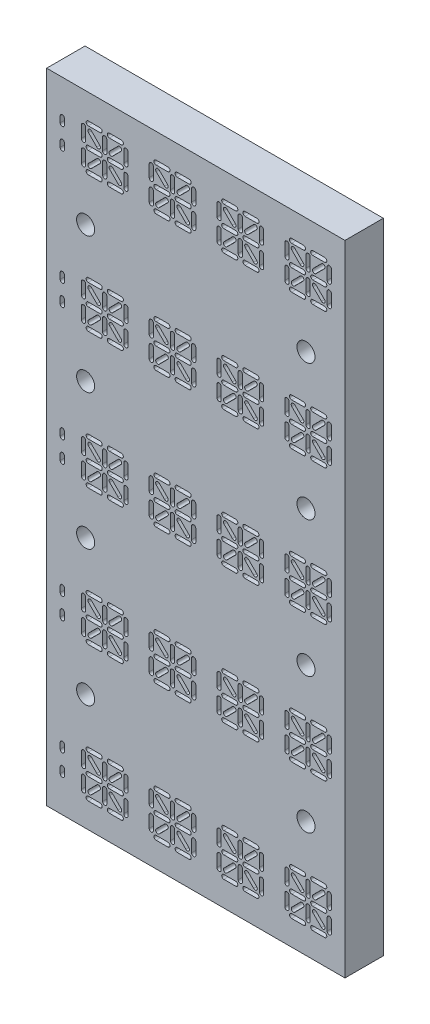
SolidWorks part; units mm, degrees
material "ABS PC"
ref_plane "Front Plane" through (0, 0, 0) normal (0, 0, 1) x (1, 0, 0)
ref_plane "Top Plane" through (0, 0, 0) normal (0, 1, 0) x (1, 0, 0)
ref_plane "Right Plane" through (0, 0, 0) normal (1, 0, 0) x (0, 0, -1)
sketch "Sketch1" plane through (0, 0, 0) normal (0, 0, 1) x (1, 0, 0)
  line L0 (265.9975, 197.0179) -> (342.1693, 194.9479) construction
  line L1 (297.418, 228.3826) -> (298.307, 228.3826) construction
  line L2 (297.418, 228.3826) -> (300.593, 228.3826) construction
  line L3 (302.371, 228.3826) -> (302.371, 231.5576) construction
  line L4 (296.7097, 229.0811) -> (296.7097, 229.9701) construction
  line L5 (296.7097, 230.8591) -> (296.7097, 234.0341) construction
  line L6 (296.7097, 234.0341) -> (299.8847, 234.0341) construction
  line L7 (296.7097, 234.0341) -> (297.0639, 234.3834) construction
  line L8 (296.7097, 234.0341) -> (297.418, 234.7326) construction
  line L9 (299.196, 231.5576) -> (300.593, 231.5576) construction
  line L10 (297.0639, 234.3834) -> (299.5404, 231.9069) construction
  line L11 (296.7097, 232.2561) -> (296.7097, 230.8591) construction
  line L12 (297.418, 231.5576) -> (296.7097, 231.5576) construction
  line L13 (299.8847, 232.2561) -> (299.196, 231.5576) construction
  line L14 (299.8945, 231.5576) -> (298.9307, 232.5165) construction
  line L15 (299.8945, 231.5576) -> (300.8534, 232.5214) construction
  line L16 (297.418, 234.7326) -> (307.578, 234.7326) construction
  line L17 (293.5347, 230.4146) -> (293.5347, 229.5256) construction
  line L18 (293.5347, 232.7006) -> (293.5347, 230.4146) construction
  line L19 (335.8892, 225.6039) -> (291.1852, 225.6039)
  line L20 (335.8892, 225.6039) -> (335.8892, 237.5114)
  line L21 (335.8892, 237.5114) -> (291.1852, 237.5114)
  line L22 (291.1852, 225.6039) -> (291.1852, 237.5114)
  line L23 (335.8892, 225.6039) -> (291.1852, 237.5114) construction
  line L24 (335.8892, 237.5114) -> (291.1852, 225.6039) construction
  line L25 (333.5397, 232.2561) -> (333.5397, 230.8591) construction
  line L26 (293.5347, 231.5576) -> (333.5397, 231.5576) construction
  line L27 (297.418, 228.3826) -> (299.196, 228.3826) construction
  line L32 (297.418, 228.7001) -> (299.196, 228.7001)
  line L33 (297.418, 228.0651) -> (299.196, 228.0651)
  line L34 (300.593, 228.3826) -> (302.371, 228.3826) construction
  line L35 (300.593, 228.7001) -> (302.371, 228.7001)
  line L36 (300.593, 228.0651) -> (302.371, 228.0651)
  line L37 (302.1155, 229.3415) -> (300.8582, 230.5987) construction
  line L38 (301.891, 229.117) -> (300.6337, 230.3742)
  line L39 (302.34, 229.566) -> (301.0827, 230.8233)
  line L40 (299.8847, 229.0811) -> (299.8847, 230.8591) construction
  line L41 (299.5672, 229.0811) -> (299.5672, 230.8591)
  line L42 (300.2022, 229.0811) -> (300.2022, 230.8591)
  line L43 (298.9356, 230.5939) -> (297.6784, 229.3366) construction
  line L44 (299.1601, 230.3694) -> (297.9029, 229.1121)
  line L45 (298.7111, 230.8184) -> (297.4539, 229.5611)
  line L46 (296.7097, 229.0811) -> (296.7097, 230.8591) construction
  line L47 (296.3922, 229.0811) -> (296.3922, 230.8591)
  line L48 (297.0272, 229.0811) -> (297.0272, 230.8591)
  line L49 (303.0597, 230.8591) -> (303.0597, 229.0811) construction
  line L50 (303.3772, 230.8591) -> (303.3772, 229.0811)
  line L51 (302.7422, 230.8591) -> (302.7422, 229.0811)
  line L52 (302.371, 231.5576) -> (300.593, 231.5576) construction
  line L53 (302.371, 231.2401) -> (300.593, 231.2401)
  line L54 (302.371, 231.8751) -> (300.593, 231.8751)
  line L55 (303.0597, 234.0341) -> (303.0597, 232.2561) construction
  line L56 (303.3772, 234.0341) -> (303.3772, 232.2561)
  line L57 (302.7422, 234.0341) -> (302.7422, 232.2561)
  line L58 (302.1106, 233.7786) -> (300.8534, 232.5214) construction
  line L59 (302.3351, 233.5541) -> (301.0779, 232.2969)
  line L60 (301.8861, 234.0031) -> (300.6289, 232.7459)
  line L61 (302.371, 234.7326) -> (300.593, 234.7326) construction
  line L62 (302.371, 234.4151) -> (300.593, 234.4151)
  line L63 (302.371, 235.0501) -> (300.593, 235.0501)
  line L64 (299.8847, 234.0341) -> (299.8847, 232.2561) construction
  line L65 (300.2022, 234.0341) -> (300.2022, 232.2561)
  line L66 (299.5672, 234.0341) -> (299.5672, 232.2561)
  line L67 (297.418, 231.5576) -> (299.196, 231.5576) construction
  line L68 (297.418, 231.8751) -> (299.196, 231.8751)
  line L69 (297.418, 231.2401) -> (299.196, 231.2401)
  line L70 (298.9307, 232.5165) -> (297.6735, 233.7737) construction
  line L71 (298.7062, 232.292) -> (297.449, 233.5492)
  line L72 (299.1552, 232.741) -> (297.898, 233.9983)
  line L73 (296.7097, 232.2561) -> (296.7097, 234.0341) construction
  line L74 (296.3922, 232.2561) -> (296.3922, 234.0341)
  line L75 (297.0272, 232.2561) -> (297.0272, 234.0341)
  line L76 (297.418, 234.7326) -> (299.196, 234.7326) construction
  line L77 (297.418, 235.0501) -> (299.196, 235.0501)
  line L78 (297.418, 234.4151) -> (299.196, 234.4151)
  line L79 (293.5347, 232.7006) -> (293.5347, 233.5896) construction
  line L80 (293.2172, 232.7006) -> (293.2172, 233.5896)
  line L81 (293.8522, 232.7006) -> (293.8522, 233.5896)
  line L82 (293.5347, 230.4146) -> (293.5347, 229.5256) construction
  line L83 (293.8522, 230.4146) -> (293.8522, 229.5256)
  line L84 (293.2172, 230.4146) -> (293.2172, 229.5256)
  line L85 (307.578, 228.3826) -> (309.356, 228.3826) construction
  line L86 (307.578, 228.7001) -> (309.356, 228.7001)
  line L87 (307.578, 228.0651) -> (309.356, 228.0651)
  line L88 (310.753, 228.3826) -> (312.531, 228.3826) construction
  line L89 (310.753, 228.7001) -> (312.531, 228.7001)
  line L90 (310.753, 228.0651) -> (312.531, 228.0651)
  line L91 (312.2755, 229.3415) -> (311.0182, 230.5987) construction
  line L92 (312.051, 229.117) -> (310.7937, 230.3742)
  line L93 (312.5, 229.566) -> (311.2427, 230.8233)
  line L94 (310.0447, 229.0811) -> (310.0447, 230.8591) construction
  line L95 (309.7272, 229.0811) -> (309.7272, 230.8591)
  line L96 (310.3622, 229.0811) -> (310.3622, 230.8591)
  line L97 (309.0956, 230.5939) -> (307.8384, 229.3366) construction
  line L98 (309.3201, 230.3694) -> (308.0629, 229.1121)
  line L99 (308.8711, 230.8184) -> (307.6139, 229.5611)
  line L100 (306.8697, 229.0811) -> (306.8697, 230.8591) construction
  line L101 (306.5522, 229.0811) -> (306.5522, 230.8591)
  line L102 (307.1872, 229.0811) -> (307.1872, 230.8591)
  line L103 (313.2197, 230.8591) -> (313.2197, 229.0811) construction
  line L104 (313.5372, 230.8591) -> (313.5372, 229.0811)
  line L105 (312.9022, 230.8591) -> (312.9022, 229.0811)
  line L106 (312.531, 231.5576) -> (310.753, 231.5576) construction
  line L107 (312.531, 231.2401) -> (310.753, 231.2401)
  line L108 (312.531, 231.8751) -> (310.753, 231.8751)
  line L109 (313.2197, 234.0341) -> (313.2197, 232.2561) construction
  line L110 (313.5372, 234.0341) -> (313.5372, 232.2561)
  line L111 (312.9022, 234.0341) -> (312.9022, 232.2561)
  line L112 (312.2706, 233.7786) -> (311.0134, 232.5214) construction
  line L113 (312.4951, 233.5541) -> (311.2379, 232.2969)
  line L114 (312.0461, 234.0031) -> (310.7889, 232.7459)
  line L115 (312.531, 234.7326) -> (310.753, 234.7326) construction
  line L116 (312.531, 234.4151) -> (310.753, 234.4151)
  line L117 (312.531, 235.0501) -> (310.753, 235.0501)
  line L118 (310.0447, 234.0341) -> (310.0447, 232.2561) construction
  line L119 (310.3622, 234.0341) -> (310.3622, 232.2561)
  line L120 (309.7272, 234.0341) -> (309.7272, 232.2561)
  line L121 (307.578, 231.5576) -> (309.356, 231.5576) construction
  line L122 (307.578, 231.8751) -> (309.356, 231.8751)
  line L123 (307.578, 231.2401) -> (309.356, 231.2401)
  line L124 (309.0907, 232.5165) -> (307.8335, 233.7737) construction
  line L125 (308.8662, 232.292) -> (307.609, 233.5492)
  line L126 (309.3152, 232.741) -> (308.058, 233.9983)
  line L127 (306.8697, 232.2561) -> (306.8697, 234.0341) construction
  line L128 (306.5522, 232.2561) -> (306.5522, 234.0341)
  line L129 (307.1872, 232.2561) -> (307.1872, 234.0341)
  line L130 (307.578, 234.7326) -> (309.356, 234.7326) construction
  line L131 (307.578, 235.0501) -> (309.356, 235.0501)
  line L132 (307.578, 234.4151) -> (309.356, 234.4151)
  line L133 (317.738, 228.3826) -> (319.516, 228.3826) construction
  line L134 (317.738, 228.7001) -> (319.516, 228.7001)
  line L135 (317.738, 228.0651) -> (319.516, 228.0651)
  line L136 (320.913, 228.3826) -> (322.691, 228.3826) construction
  line L137 (320.913, 228.7001) -> (322.691, 228.7001)
  line L138 (320.913, 228.0651) -> (322.691, 228.0651)
  line L139 (322.4355, 229.3415) -> (321.1782, 230.5987) construction
  line L140 (322.211, 229.117) -> (320.9537, 230.3742)
  line L141 (322.66, 229.566) -> (321.4027, 230.8233)
  line L142 (320.2047, 229.0811) -> (320.2047, 230.8591) construction
  line L143 (319.8872, 229.0811) -> (319.8872, 230.8591)
  line L144 (320.5222, 229.0811) -> (320.5222, 230.8591)
  line L145 (319.2556, 230.5939) -> (317.9984, 229.3366) construction
  line L146 (319.4801, 230.3694) -> (318.2229, 229.1121)
  line L147 (319.0311, 230.8184) -> (317.7739, 229.5611)
  line L148 (317.0297, 229.0811) -> (317.0297, 230.8591) construction
  line L149 (316.7122, 229.0811) -> (316.7122, 230.8591)
  line L150 (317.3472, 229.0811) -> (317.3472, 230.8591)
  line L151 (323.3797, 230.8591) -> (323.3797, 229.0811) construction
  line L152 (323.6972, 230.8591) -> (323.6972, 229.0811)
  line L153 (323.0622, 230.8591) -> (323.0622, 229.0811)
  line L154 (322.691, 231.5576) -> (320.913, 231.5576) construction
  line L155 (322.691, 231.2401) -> (320.913, 231.2401)
  line L156 (322.691, 231.8751) -> (320.913, 231.8751)
  line L157 (323.3797, 234.0341) -> (323.3797, 232.2561) construction
  line L158 (323.6972, 234.0341) -> (323.6972, 232.2561)
  line L159 (323.0622, 234.0341) -> (323.0622, 232.2561)
  line L160 (322.4306, 233.7786) -> (321.1734, 232.5214) construction
  line L161 (322.6551, 233.5541) -> (321.3979, 232.2969)
  line L162 (322.2061, 234.0031) -> (320.9489, 232.7459)
  line L163 (322.691, 234.7326) -> (320.913, 234.7326) construction
  line L164 (322.691, 234.4151) -> (320.913, 234.4151)
  line L165 (322.691, 235.0501) -> (320.913, 235.0501)
  line L166 (320.2047, 234.0341) -> (320.2047, 232.2561) construction
  line L167 (320.5222, 234.0341) -> (320.5222, 232.2561)
  line L168 (319.8872, 234.0341) -> (319.8872, 232.2561)
  line L169 (317.738, 231.5576) -> (319.516, 231.5576) construction
  line L170 (317.738, 231.8751) -> (319.516, 231.8751)
  line L171 (317.738, 231.2401) -> (319.516, 231.2401)
  line L172 (319.2507, 232.5165) -> (317.9935, 233.7737) construction
  line L173 (319.0262, 232.292) -> (317.769, 233.5492)
  line L174 (319.4752, 232.741) -> (318.218, 233.9983)
  line L175 (317.0297, 232.2561) -> (317.0297, 234.0341) construction
  line L176 (316.7122, 232.2561) -> (316.7122, 234.0341)
  line L177 (317.3472, 232.2561) -> (317.3472, 234.0341)
  line L178 (317.738, 234.7326) -> (319.516, 234.7326) construction
  line L179 (317.738, 235.0501) -> (319.516, 235.0501)
  line L180 (317.738, 234.4151) -> (319.516, 234.4151)
  line L181 (327.898, 228.3826) -> (329.676, 228.3826) construction
  line L182 (327.898, 228.7001) -> (329.676, 228.7001)
  line L183 (327.898, 228.0651) -> (329.676, 228.0651)
  line L184 (331.073, 228.3826) -> (332.851, 228.3826) construction
  line L185 (331.073, 228.7001) -> (332.851, 228.7001)
  line L186 (331.073, 228.0651) -> (332.851, 228.0651)
  line L187 (332.5955, 229.3415) -> (331.3382, 230.5987) construction
  line L188 (332.371, 229.117) -> (331.1137, 230.3742)
  line L189 (332.82, 229.566) -> (331.5627, 230.8233)
  line L190 (330.3647, 229.0811) -> (330.3647, 230.8591) construction
  line L191 (330.0472, 229.0811) -> (330.0472, 230.8591)
  line L192 (330.6822, 229.0811) -> (330.6822, 230.8591)
  line L193 (329.4156, 230.5939) -> (328.1584, 229.3366) construction
  line L194 (329.6401, 230.3694) -> (328.3829, 229.1121)
  line L195 (329.1911, 230.8184) -> (327.9339, 229.5611)
  line L196 (327.1897, 229.0811) -> (327.1897, 230.8591) construction
  line L197 (326.8722, 229.0811) -> (326.8722, 230.8591)
  line L198 (327.5072, 229.0811) -> (327.5072, 230.8591)
  line L199 (333.5397, 230.8591) -> (333.5397, 229.0811) construction
  line L200 (333.8572, 230.8591) -> (333.8572, 229.0811)
  line L201 (333.2222, 230.8591) -> (333.2222, 229.0811)
  line L202 (332.851, 231.5576) -> (331.073, 231.5576) construction
  line L203 (332.851, 231.2401) -> (331.073, 231.2401)
  line L204 (332.851, 231.8751) -> (331.073, 231.8751)
  line L205 (333.5397, 234.0341) -> (333.5397, 232.2561) construction
  line L206 (333.8572, 234.0341) -> (333.8572, 232.2561)
  line L207 (333.2222, 234.0341) -> (333.2222, 232.2561)
  line L208 (332.5906, 233.7786) -> (331.3334, 232.5214) construction
  line L209 (332.8151, 233.5541) -> (331.5579, 232.2969)
  line L210 (332.3661, 234.0031) -> (331.1089, 232.7459)
  line L211 (332.851, 234.7326) -> (331.073, 234.7326) construction
  line L212 (332.851, 234.4151) -> (331.073, 234.4151)
  line L213 (332.851, 235.0501) -> (331.073, 235.0501)
  line L214 (330.3647, 234.0341) -> (330.3647, 232.2561) construction
  line L215 (330.6822, 234.0341) -> (330.6822, 232.2561)
  line L216 (330.0472, 234.0341) -> (330.0472, 232.2561)
  line L217 (327.898, 231.5576) -> (329.676, 231.5576) construction
  line L218 (327.898, 231.8751) -> (329.676, 231.8751)
  line L219 (327.898, 231.2401) -> (329.676, 231.2401)
  line L220 (329.4107, 232.5165) -> (328.1535, 233.7737) construction
  line L221 (329.1862, 232.292) -> (327.929, 233.5492)
  line L222 (329.6352, 232.741) -> (328.378, 233.9983)
  line L223 (327.1897, 232.2561) -> (327.1897, 234.0341) construction
  line L224 (326.8722, 232.2561) -> (326.8722, 234.0341)
  line L225 (327.5072, 232.2561) -> (327.5072, 234.0341)
  line L226 (327.898, 234.7326) -> (329.676, 234.7326) construction
  line L227 (327.898, 235.0501) -> (329.676, 235.0501)
  line L228 (327.898, 234.4151) -> (329.676, 234.4151)
  line L229 (296.7097, 229.0811) -> (306.8697, 229.0811) construction
  circle A0 centre (297.418, 228.3826) radius 0.3175 construction
  circle A3 centre (298.307, 228.3826) radius 0.3175 construction
  circle A4 centre (299.196, 228.3826) radius 0.3175 construction
  circle A5 centre (300.593, 228.3826) radius 0.3175 construction
  circle A6 centre (301.482, 228.3826) radius 0.3175 construction
  circle A7 centre (302.371, 228.3826) radius 0.3175 construction
  circle A8 centre (302.371, 231.5576) radius 0.3175 construction
  circle A9 centre (301.482, 231.5576) radius 0.3175 construction
  circle A10 centre (300.593, 231.5576) radius 0.3175 construction
  circle A11 centre (299.196, 231.5576) radius 0.3175 construction
  circle A12 centre (298.307, 231.5576) radius 0.3175 construction
  circle A13 centre (297.418, 231.5576) radius 0.3175 construction
  circle A14 centre (302.371, 234.7326) radius 0.3175 construction
  circle A15 centre (301.482, 234.7326) radius 0.3175 construction
  circle A16 centre (300.593, 234.7326) radius 0.3175 construction
  circle A17 centre (299.196, 234.7326) radius 0.3175 construction
  circle A18 centre (298.307, 234.7326) radius 0.3175 construction
  circle A19 centre (297.418, 234.7326) radius 0.3175 construction
  circle A20 centre (296.7097, 229.0811) radius 0.3175 construction
  circle A21 centre (296.7097, 229.9701) radius 0.3175 construction
  circle A22 centre (296.7097, 230.8591) radius 0.3175 construction
  circle A23 centre (296.7097, 234.0341) radius 0.3175 construction
  circle A24 centre (296.7097, 233.1451) radius 0.3175 construction
  circle A25 centre (296.7097, 232.2561) radius 0.3175 construction
  circle A26 centre (299.8847, 234.0341) radius 0.3175 construction
  circle A27 centre (299.8847, 233.1451) radius 0.3175 construction
  circle A28 centre (299.8847, 232.2561) radius 0.3175 construction
  circle A29 centre (299.8847, 230.8591) radius 0.3175 construction
  circle A30 centre (299.8847, 229.9701) radius 0.3175 construction
  circle A31 centre (299.8847, 229.0811) radius 0.3175 construction
  circle A32 centre (297.6735, 233.7737) radius 0.3175 construction
  circle A33 centre (298.3021, 233.1451) radius 0.3175 construction
  circle A34 centre (298.9307, 232.5165) radius 0.3175 construction
  circle A35 centre (303.0597, 234.0341) radius 0.3175 construction
  circle A36 centre (303.0597, 233.1451) radius 0.3175 construction
  circle A37 centre (303.0597, 232.2561) radius 0.3175 construction
  circle A38 centre (303.0597, 230.8591) radius 0.3175 construction
  circle A39 centre (303.0597, 229.9701) radius 0.3175 construction
  circle A40 centre (303.0597, 229.0811) radius 0.3175 construction
  circle A41 centre (300.8534, 232.5214) radius 0.3175 construction
  circle A42 centre (301.482, 233.15) radius 0.3175 construction
  circle A43 centre (302.1106, 233.7786) radius 0.3175 construction
  circle A44 centre (300.8582, 230.5987) radius 0.3175 construction
  circle A45 centre (301.4869, 229.9701) radius 0.3175 construction
  circle A46 centre (302.1155, 229.3415) radius 0.3175 construction
  circle A47 centre (298.9356, 230.5939) radius 0.3175 construction
  circle A48 centre (298.307, 229.9653) radius 0.3175 construction
  circle A49 centre (297.6784, 229.3366) radius 0.3175 construction
  circle A50 centre (307.578, 234.7326) radius 0.3175 construction
  circle A51 centre (306.8697, 234.0341) radius 0.3175 construction
  circle A52 centre (306.8697, 233.1451) radius 0.3175 construction
  circle A53 centre (306.8697, 232.2561) radius 0.3175 construction
  circle A54 centre (308.467, 234.7326) radius 0.3175 construction
  circle A55 centre (309.356, 234.7326) radius 0.3175 construction
  circle A56 centre (310.753, 234.7326) radius 0.3175 construction
  circle A57 centre (311.642, 234.7326) radius 0.3175 construction
  circle A58 centre (312.531, 234.7326) radius 0.3175 construction
  circle A59 centre (313.2197, 234.0341) radius 0.3175 construction
  circle A60 centre (313.2197, 233.1451) radius 0.3175 construction
  circle A61 centre (313.2197, 232.2561) radius 0.3175 construction
  circle A62 centre (313.2197, 230.8591) radius 0.3175 construction
  circle A63 centre (313.2197, 229.9701) radius 0.3175 construction
  circle A64 centre (313.2197, 229.0811) radius 0.3175 construction
  circle A65 centre (312.531, 228.3826) radius 0.3175 construction
  circle A66 centre (311.642, 228.3826) radius 0.3175 construction
  circle A67 centre (310.753, 228.3826) radius 0.3175 construction
  circle A68 centre (309.356, 228.3826) radius 0.3175 construction
  circle A69 centre (308.467, 228.3826) radius 0.3175 construction
  circle A70 centre (307.578, 228.3826) radius 0.3175 construction
  circle A71 centre (306.8697, 229.0811) radius 0.3175 construction
  circle A72 centre (306.8697, 229.9701) radius 0.3175 construction
  circle A73 centre (306.8697, 230.8591) radius 0.3175 construction
  circle A74 centre (307.578, 231.5576) radius 0.3175 construction
  circle A75 centre (308.467, 231.5576) radius 0.3175 construction
  circle A76 centre (309.356, 231.5576) radius 0.3175 construction
  circle A77 centre (310.753, 231.5576) radius 0.3175 construction
  circle A78 centre (311.642, 231.5576) radius 0.3175 construction
  circle A79 centre (312.531, 231.5576) radius 0.3175 construction
  circle A80 centre (312.2706, 233.7786) radius 0.3175 construction
  circle A81 centre (311.642, 233.15) radius 0.3175 construction
  circle A82 centre (311.0134, 232.5214) radius 0.3175 construction
  circle A83 centre (310.0447, 232.2561) radius 0.3175 construction
  circle A84 centre (310.0447, 233.1451) radius 0.3175 construction
  circle A85 centre (310.0447, 234.0341) radius 0.3175 construction
  circle A86 centre (309.0907, 232.5165) radius 0.3175 construction
  circle A87 centre (308.4621, 233.1451) radius 0.3175 construction
  circle A88 centre (307.8335, 233.7737) radius 0.3175 construction
  circle A89 centre (307.8384, 229.3366) radius 0.3175 construction
  circle A90 centre (308.467, 229.9653) radius 0.3175 construction
  circle A91 centre (309.0956, 230.5939) radius 0.3175 construction
  circle A92 centre (310.0447, 230.8591) radius 0.3175 construction
  circle A93 centre (310.0447, 229.9701) radius 0.3175 construction
  circle A94 centre (310.0447, 229.0811) radius 0.3175 construction
  circle A95 centre (312.2755, 229.3415) radius 0.3175 construction
  circle A96 centre (311.6469, 229.9701) radius 0.3175 construction
  circle A97 centre (311.0182, 230.5987) radius 0.3175 construction
  circle A98 centre (317.738, 234.7326) radius 0.3175 construction
  circle A99 centre (317.0297, 234.0341) radius 0.3175 construction
  circle A100 centre (317.0297, 233.1451) radius 0.3175 construction
  circle A101 centre (317.0297, 232.2561) radius 0.3175 construction
  circle A102 centre (318.627, 234.7326) radius 0.3175 construction
  circle A103 centre (319.516, 234.7326) radius 0.3175 construction
  circle A104 centre (320.913, 234.7326) radius 0.3175 construction
  circle A105 centre (321.802, 234.7326) radius 0.3175 construction
  circle A106 centre (322.691, 234.7326) radius 0.3175 construction
  circle A107 centre (323.3797, 234.0341) radius 0.3175 construction
  circle A108 centre (323.3797, 233.1451) radius 0.3175 construction
  circle A109 centre (323.3797, 232.2561) radius 0.3175 construction
  circle A110 centre (323.3797, 230.8591) radius 0.3175 construction
  circle A111 centre (323.3797, 229.9701) radius 0.3175 construction
  circle A112 centre (323.3797, 229.0811) radius 0.3175 construction
  circle A113 centre (322.691, 228.3826) radius 0.3175 construction
  circle A114 centre (321.802, 228.3826) radius 0.3175 construction
  circle A115 centre (320.913, 228.3826) radius 0.3175 construction
  circle A116 centre (319.516, 228.3826) radius 0.3175 construction
  circle A117 centre (318.627, 228.3826) radius 0.3175 construction
  circle A118 centre (317.738, 228.3826) radius 0.3175 construction
  circle A119 centre (317.0297, 229.0811) radius 0.3175 construction
  circle A120 centre (317.0297, 229.9701) radius 0.3175 construction
  circle A121 centre (317.0297, 230.8591) radius 0.3175 construction
  circle A122 centre (317.738, 231.5576) radius 0.3175 construction
  circle A123 centre (318.627, 231.5576) radius 0.3175 construction
  circle A124 centre (319.516, 231.5576) radius 0.3175 construction
  circle A125 centre (320.913, 231.5576) radius 0.3175 construction
  circle A126 centre (321.802, 231.5576) radius 0.3175 construction
  circle A127 centre (322.691, 231.5576) radius 0.3175 construction
  circle A128 centre (322.4306, 233.7786) radius 0.3175 construction
  circle A129 centre (321.802, 233.15) radius 0.3175 construction
  circle A130 centre (321.1734, 232.5214) radius 0.3175 construction
  circle A131 centre (320.2047, 232.2561) radius 0.3175 construction
  circle A132 centre (320.2047, 233.1451) radius 0.3175 construction
  circle A133 centre (320.2047, 234.0341) radius 0.3175 construction
  circle A134 centre (319.2507, 232.5165) radius 0.3175 construction
  circle A135 centre (318.6221, 233.1451) radius 0.3175 construction
  circle A136 centre (317.9935, 233.7737) radius 0.3175 construction
  circle A137 centre (317.9984, 229.3366) radius 0.3175 construction
  circle A138 centre (318.627, 229.9653) radius 0.3175 construction
  circle A139 centre (319.2556, 230.5939) radius 0.3175 construction
  circle A140 centre (320.2047, 230.8591) radius 0.3175 construction
  circle A141 centre (320.2047, 229.9701) radius 0.3175 construction
  circle A142 centre (320.2047, 229.0811) radius 0.3175 construction
  circle A143 centre (322.4355, 229.3415) radius 0.3175 construction
  circle A144 centre (321.8069, 229.9701) radius 0.3175 construction
  circle A145 centre (321.1782, 230.5987) radius 0.3175 construction
  circle A146 centre (327.898, 234.7326) radius 0.3175 construction
  circle A147 centre (327.1897, 234.0341) radius 0.3175 construction
  circle A148 centre (327.1897, 233.1451) radius 0.3175 construction
  circle A149 centre (327.1897, 232.2561) radius 0.3175 construction
  circle A150 centre (328.787, 234.7326) radius 0.3175 construction
  circle A151 centre (329.676, 234.7326) radius 0.3175 construction
  circle A152 centre (331.073, 234.7326) radius 0.3175 construction
  circle A153 centre (331.962, 234.7326) radius 0.3175 construction
  circle A154 centre (332.851, 234.7326) radius 0.3175 construction
  circle A155 centre (333.5397, 234.0341) radius 0.3175 construction
  circle A156 centre (333.5397, 233.1451) radius 0.3175 construction
  circle A157 centre (333.5397, 232.2561) radius 0.3175 construction
  circle A158 centre (333.5397, 230.8591) radius 0.3175 construction
  circle A159 centre (333.5397, 229.9701) radius 0.3175 construction
  circle A160 centre (333.5397, 229.0811) radius 0.3175 construction
  circle A161 centre (332.851, 228.3826) radius 0.3175 construction
  circle A162 centre (331.962, 228.3826) radius 0.3175 construction
  circle A163 centre (331.073, 228.3826) radius 0.3175 construction
  circle A164 centre (329.676, 228.3826) radius 0.3175 construction
  circle A165 centre (328.787, 228.3826) radius 0.3175 construction
  circle A166 centre (327.898, 228.3826) radius 0.3175 construction
  circle A167 centre (327.1897, 229.0811) radius 0.3175 construction
  circle A168 centre (327.1897, 229.9701) radius 0.3175 construction
  circle A169 centre (327.1897, 230.8591) radius 0.3175 construction
  circle A170 centre (327.898, 231.5576) radius 0.3175 construction
  circle A171 centre (328.787, 231.5576) radius 0.3175 construction
  circle A172 centre (329.676, 231.5576) radius 0.3175 construction
  circle A173 centre (331.073, 231.5576) radius 0.3175 construction
  circle A174 centre (331.962, 231.5576) radius 0.3175 construction
  circle A175 centre (332.851, 231.5576) radius 0.3175 construction
  circle A176 centre (332.5906, 233.7786) radius 0.3175 construction
  circle A177 centre (331.962, 233.15) radius 0.3175 construction
  circle A178 centre (331.3334, 232.5214) radius 0.3175 construction
  circle A179 centre (330.3647, 232.2561) radius 0.3175 construction
  circle A180 centre (330.3647, 233.1451) radius 0.3175 construction
  circle A181 centre (330.3647, 234.0341) radius 0.3175 construction
  circle A182 centre (329.4107, 232.5165) radius 0.3175 construction
  circle A183 centre (328.7821, 233.1451) radius 0.3175 construction
  circle A184 centre (328.1535, 233.7737) radius 0.3175 construction
  circle A185 centre (328.1584, 229.3366) radius 0.3175 construction
  circle A186 centre (328.787, 229.9653) radius 0.3175 construction
  circle A187 centre (329.4156, 230.5939) radius 0.3175 construction
  circle A188 centre (330.3647, 230.8591) radius 0.3175 construction
  circle A189 centre (330.3647, 229.9701) radius 0.3175 construction
  circle A190 centre (330.3647, 229.0811) radius 0.3175 construction
  circle A191 centre (332.5955, 229.3415) radius 0.3175 construction
  circle A192 centre (331.9669, 229.9701) radius 0.3175 construction
  circle A193 centre (331.3382, 230.5987) radius 0.3175 construction
  circle A194 centre (293.5347, 229.5256) radius 0.3175 construction
  circle A195 centre (293.5347, 230.4146) radius 0.3175 construction
  circle A196 centre (293.5347, 233.5896) radius 0.3175 construction
  circle A197 centre (293.5347, 232.7006) radius 0.3175 construction
  arc A198 (297.418, 228.7001) -> (297.418, 228.0651) centre (297.418, 228.3826) ccw
  arc A199 (299.196, 228.0651) -> (299.196, 228.7001) centre (299.196, 228.3826) ccw
  arc A200 (300.593, 228.7001) -> (300.593, 228.0651) centre (300.593, 228.3826) ccw
  arc A201 (302.371, 228.0651) -> (302.371, 228.7001) centre (302.371, 228.3826) ccw
  arc A202 (301.891, 229.117) -> (302.34, 229.566) centre (302.1155, 229.3415) ccw
  arc A203 (301.0827, 230.8233) -> (300.6337, 230.3742) centre (300.8582, 230.5987) ccw
  arc A204 (299.5672, 229.0811) -> (300.2022, 229.0811) centre (299.8847, 229.0811) ccw
  arc A205 (300.2022, 230.8591) -> (299.5672, 230.8591) centre (299.8847, 230.8591) ccw
  arc A206 (299.1601, 230.3694) -> (298.7111, 230.8184) centre (298.9356, 230.5939) ccw
  arc A207 (297.4539, 229.5611) -> (297.9029, 229.1121) centre (297.6784, 229.3366) ccw
  arc A208 (296.3922, 229.0811) -> (297.0272, 229.0811) centre (296.7097, 229.0811) ccw
  arc A209 (297.0272, 230.8591) -> (296.3922, 230.8591) centre (296.7097, 230.8591) ccw
  arc A210 (303.3772, 230.8591) -> (302.7422, 230.8591) centre (303.0597, 230.8591) ccw
  arc A211 (302.7422, 229.0811) -> (303.3772, 229.0811) centre (303.0597, 229.0811) ccw
  arc A212 (302.371, 231.2401) -> (302.371, 231.8751) centre (302.371, 231.5576) ccw
  arc A213 (300.593, 231.8751) -> (300.593, 231.2401) centre (300.593, 231.5576) ccw
  arc A214 (303.3772, 234.0341) -> (302.7422, 234.0341) centre (303.0597, 234.0341) ccw
  arc A215 (302.7422, 232.2561) -> (303.3772, 232.2561) centre (303.0597, 232.2561) ccw
  arc A216 (302.3351, 233.5541) -> (301.8861, 234.0031) centre (302.1106, 233.7786) ccw
  arc A217 (300.6289, 232.7459) -> (301.0779, 232.2969) centre (300.8534, 232.5214) ccw
  arc A218 (302.371, 234.4151) -> (302.371, 235.0501) centre (302.371, 234.7326) ccw
  arc A219 (300.593, 235.0501) -> (300.593, 234.4151) centre (300.593, 234.7326) ccw
  arc A220 (300.2022, 234.0341) -> (299.5672, 234.0341) centre (299.8847, 234.0341) ccw
  arc A221 (299.5672, 232.2561) -> (300.2022, 232.2561) centre (299.8847, 232.2561) ccw
  arc A222 (297.418, 231.8751) -> (297.418, 231.2401) centre (297.418, 231.5576) ccw
  arc A223 (299.196, 231.2401) -> (299.196, 231.8751) centre (299.196, 231.5576) ccw
  arc A224 (298.7062, 232.292) -> (299.1552, 232.741) centre (298.9307, 232.5165) ccw
  arc A225 (297.898, 233.9983) -> (297.449, 233.5492) centre (297.6735, 233.7737) ccw
  arc A226 (296.3922, 232.2561) -> (297.0272, 232.2561) centre (296.7097, 232.2561) ccw
  arc A227 (297.0272, 234.0341) -> (296.3922, 234.0341) centre (296.7097, 234.0341) ccw
  arc A228 (297.418, 235.0501) -> (297.418, 234.4151) centre (297.418, 234.7326) ccw
  arc A229 (299.196, 234.4151) -> (299.196, 235.0501) centre (299.196, 234.7326) ccw
  arc A230 (293.2172, 232.7006) -> (293.8522, 232.7006) centre (293.5347, 232.7006) ccw
  arc A231 (293.8522, 233.5896) -> (293.2172, 233.5896) centre (293.5347, 233.5896) ccw
  arc A232 (293.8522, 230.4146) -> (293.2172, 230.4146) centre (293.5347, 230.4146) ccw
  arc A233 (293.2172, 229.5256) -> (293.8522, 229.5256) centre (293.5347, 229.5256) ccw
  arc A234 (307.578, 228.7001) -> (307.578, 228.0651) centre (307.578, 228.3826) ccw
  arc A235 (309.356, 228.0651) -> (309.356, 228.7001) centre (309.356, 228.3826) ccw
  arc A236 (310.753, 228.7001) -> (310.753, 228.0651) centre (310.753, 228.3826) ccw
  arc A237 (312.531, 228.0651) -> (312.531, 228.7001) centre (312.531, 228.3826) ccw
  arc A238 (312.051, 229.117) -> (312.5, 229.566) centre (312.2755, 229.3415) ccw
  arc A239 (311.2427, 230.8233) -> (310.7937, 230.3742) centre (311.0182, 230.5987) ccw
  arc A240 (309.7272, 229.0811) -> (310.3622, 229.0811) centre (310.0447, 229.0811) ccw
  arc A241 (310.3622, 230.8591) -> (309.7272, 230.8591) centre (310.0447, 230.8591) ccw
  arc A242 (309.3201, 230.3694) -> (308.8711, 230.8184) centre (309.0956, 230.5939) ccw
  arc A243 (307.6139, 229.5611) -> (308.0629, 229.1121) centre (307.8384, 229.3366) ccw
  arc A244 (306.5522, 229.0811) -> (307.1872, 229.0811) centre (306.8697, 229.0811) ccw
  arc A245 (307.1872, 230.8591) -> (306.5522, 230.8591) centre (306.8697, 230.8591) ccw
  arc A246 (313.5372, 230.8591) -> (312.9022, 230.8591) centre (313.2197, 230.8591) ccw
  arc A247 (312.9022, 229.0811) -> (313.5372, 229.0811) centre (313.2197, 229.0811) ccw
  arc A248 (312.531, 231.2401) -> (312.531, 231.8751) centre (312.531, 231.5576) ccw
  arc A249 (310.753, 231.8751) -> (310.753, 231.2401) centre (310.753, 231.5576) ccw
  arc A250 (313.5372, 234.0341) -> (312.9022, 234.0341) centre (313.2197, 234.0341) ccw
  arc A251 (312.9022, 232.2561) -> (313.5372, 232.2561) centre (313.2197, 232.2561) ccw
  arc A252 (312.4951, 233.5541) -> (312.0461, 234.0031) centre (312.2706, 233.7786) ccw
  arc A253 (310.7889, 232.7459) -> (311.2379, 232.2969) centre (311.0134, 232.5214) ccw
  arc A254 (312.531, 234.4151) -> (312.531, 235.0501) centre (312.531, 234.7326) ccw
  arc A255 (310.753, 235.0501) -> (310.753, 234.4151) centre (310.753, 234.7326) ccw
  arc A256 (310.3622, 234.0341) -> (309.7272, 234.0341) centre (310.0447, 234.0341) ccw
  arc A257 (309.7272, 232.2561) -> (310.3622, 232.2561) centre (310.0447, 232.2561) ccw
  arc A258 (307.578, 231.8751) -> (307.578, 231.2401) centre (307.578, 231.5576) ccw
  arc A259 (309.356, 231.2401) -> (309.356, 231.8751) centre (309.356, 231.5576) ccw
  arc A260 (308.8662, 232.292) -> (309.3152, 232.741) centre (309.0907, 232.5165) ccw
  arc A261 (308.058, 233.9983) -> (307.609, 233.5492) centre (307.8335, 233.7737) ccw
  arc A262 (306.5522, 232.2561) -> (307.1872, 232.2561) centre (306.8697, 232.2561) ccw
  arc A263 (307.1872, 234.0341) -> (306.5522, 234.0341) centre (306.8697, 234.0341) ccw
  arc A264 (307.578, 235.0501) -> (307.578, 234.4151) centre (307.578, 234.7326) ccw
  arc A265 (309.356, 234.4151) -> (309.356, 235.0501) centre (309.356, 234.7326) ccw
  arc A266 (317.738, 228.7001) -> (317.738, 228.0651) centre (317.738, 228.3826) ccw
  arc A267 (319.516, 228.0651) -> (319.516, 228.7001) centre (319.516, 228.3826) ccw
  arc A268 (320.913, 228.7001) -> (320.913, 228.0651) centre (320.913, 228.3826) ccw
  arc A269 (322.691, 228.0651) -> (322.691, 228.7001) centre (322.691, 228.3826) ccw
  arc A270 (322.211, 229.117) -> (322.66, 229.566) centre (322.4355, 229.3415) ccw
  arc A271 (321.4027, 230.8233) -> (320.9537, 230.3742) centre (321.1782, 230.5987) ccw
  arc A272 (319.8872, 229.0811) -> (320.5222, 229.0811) centre (320.2047, 229.0811) ccw
  arc A273 (320.5222, 230.8591) -> (319.8872, 230.8591) centre (320.2047, 230.8591) ccw
  arc A274 (319.4801, 230.3694) -> (319.0311, 230.8184) centre (319.2556, 230.5939) ccw
  arc A275 (317.7739, 229.5611) -> (318.2229, 229.1121) centre (317.9984, 229.3366) ccw
  arc A276 (316.7122, 229.0811) -> (317.3472, 229.0811) centre (317.0297, 229.0811) ccw
  arc A277 (317.3472, 230.8591) -> (316.7122, 230.8591) centre (317.0297, 230.8591) ccw
  arc A278 (323.6972, 230.8591) -> (323.0622, 230.8591) centre (323.3797, 230.8591) ccw
  arc A279 (323.0622, 229.0811) -> (323.6972, 229.0811) centre (323.3797, 229.0811) ccw
  arc A280 (322.691, 231.2401) -> (322.691, 231.8751) centre (322.691, 231.5576) ccw
  arc A281 (320.913, 231.8751) -> (320.913, 231.2401) centre (320.913, 231.5576) ccw
  arc A282 (323.6972, 234.0341) -> (323.0622, 234.0341) centre (323.3797, 234.0341) ccw
  arc A283 (323.0622, 232.2561) -> (323.6972, 232.2561) centre (323.3797, 232.2561) ccw
  arc A284 (322.6551, 233.5541) -> (322.2061, 234.0031) centre (322.4306, 233.7786) ccw
  arc A285 (320.9489, 232.7459) -> (321.3979, 232.2969) centre (321.1734, 232.5214) ccw
  arc A286 (322.691, 234.4151) -> (322.691, 235.0501) centre (322.691, 234.7326) ccw
  arc A287 (320.913, 235.0501) -> (320.913, 234.4151) centre (320.913, 234.7326) ccw
  arc A288 (320.5222, 234.0341) -> (319.8872, 234.0341) centre (320.2047, 234.0341) ccw
  arc A289 (319.8872, 232.2561) -> (320.5222, 232.2561) centre (320.2047, 232.2561) ccw
  arc A290 (317.738, 231.8751) -> (317.738, 231.2401) centre (317.738, 231.5576) ccw
  arc A291 (319.516, 231.2401) -> (319.516, 231.8751) centre (319.516, 231.5576) ccw
  arc A292 (319.0262, 232.292) -> (319.4752, 232.741) centre (319.2507, 232.5165) ccw
  arc A293 (318.218, 233.9983) -> (317.769, 233.5492) centre (317.9935, 233.7737) ccw
  arc A294 (316.7122, 232.2561) -> (317.3472, 232.2561) centre (317.0297, 232.2561) ccw
  arc A295 (317.3472, 234.0341) -> (316.7122, 234.0341) centre (317.0297, 234.0341) ccw
  arc A296 (317.738, 235.0501) -> (317.738, 234.4151) centre (317.738, 234.7326) ccw
  arc A297 (319.516, 234.4151) -> (319.516, 235.0501) centre (319.516, 234.7326) ccw
  arc A298 (327.898, 228.7001) -> (327.898, 228.0651) centre (327.898, 228.3826) ccw
  arc A299 (329.676, 228.0651) -> (329.676, 228.7001) centre (329.676, 228.3826) ccw
  arc A300 (331.073, 228.7001) -> (331.073, 228.0651) centre (331.073, 228.3826) ccw
  arc A301 (332.851, 228.0651) -> (332.851, 228.7001) centre (332.851, 228.3826) ccw
  arc A302 (332.371, 229.117) -> (332.82, 229.566) centre (332.5955, 229.3415) ccw
  arc A303 (331.5627, 230.8233) -> (331.1137, 230.3742) centre (331.3382, 230.5987) ccw
  arc A304 (330.0472, 229.0811) -> (330.6822, 229.0811) centre (330.3647, 229.0811) ccw
  arc A305 (330.6822, 230.8591) -> (330.0472, 230.8591) centre (330.3647, 230.8591) ccw
  arc A306 (329.6401, 230.3694) -> (329.1911, 230.8184) centre (329.4156, 230.5939) ccw
  arc A307 (327.9339, 229.5611) -> (328.3829, 229.1121) centre (328.1584, 229.3366) ccw
  arc A308 (326.8722, 229.0811) -> (327.5072, 229.0811) centre (327.1897, 229.0811) ccw
  arc A309 (327.5072, 230.8591) -> (326.8722, 230.8591) centre (327.1897, 230.8591) ccw
  arc A310 (333.8572, 230.8591) -> (333.2222, 230.8591) centre (333.5397, 230.8591) ccw
  arc A311 (333.2222, 229.0811) -> (333.8572, 229.0811) centre (333.5397, 229.0811) ccw
  arc A312 (332.851, 231.2401) -> (332.851, 231.8751) centre (332.851, 231.5576) ccw
  arc A313 (331.073, 231.8751) -> (331.073, 231.2401) centre (331.073, 231.5576) ccw
  arc A314 (333.8572, 234.0341) -> (333.2222, 234.0341) centre (333.5397, 234.0341) ccw
  arc A315 (333.2222, 232.2561) -> (333.8572, 232.2561) centre (333.5397, 232.2561) ccw
  arc A316 (332.8151, 233.5541) -> (332.3661, 234.0031) centre (332.5906, 233.7786) ccw
  arc A317 (331.1089, 232.7459) -> (331.5579, 232.2969) centre (331.3334, 232.5214) ccw
  arc A318 (332.851, 234.4151) -> (332.851, 235.0501) centre (332.851, 234.7326) ccw
  arc A319 (331.073, 235.0501) -> (331.073, 234.4151) centre (331.073, 234.7326) ccw
  arc A320 (330.6822, 234.0341) -> (330.0472, 234.0341) centre (330.3647, 234.0341) ccw
  arc A321 (330.0472, 232.2561) -> (330.6822, 232.2561) centre (330.3647, 232.2561) ccw
  arc A322 (327.898, 231.8751) -> (327.898, 231.2401) centre (327.898, 231.5576) ccw
  arc A323 (329.676, 231.2401) -> (329.676, 231.8751) centre (329.676, 231.5576) ccw
  arc A324 (329.1862, 232.292) -> (329.6352, 232.741) centre (329.4107, 232.5165) ccw
  arc A325 (328.378, 233.9983) -> (327.929, 233.5492) centre (328.1535, 233.7737) ccw
  arc A326 (326.8722, 232.2561) -> (327.5072, 232.2561) centre (327.1897, 232.2561) ccw
  arc A327 (327.5072, 234.0341) -> (326.8722, 234.0341) centre (327.1897, 234.0341) ccw
  arc A328 (327.898, 235.0501) -> (327.898, 234.4151) centre (327.898, 234.7326) ccw
  arc A329 (329.676, 234.4151) -> (329.676, 235.0501) centre (329.676, 234.7326) ccw
  point P17 (298.307, 228.3826)
  point P81 (299.8945, 231.5576)
  point P96 (298.3021, 233.1451)
  point P410 (293.5347, 229.9701)
  point P411 (313.5372, 231.5576)
  point P422 (313.5372, 231.5576)
  point P426 (301.482, 228.3826)
  point P431 (301.4869, 229.9701)
  point P436 (299.8847, 229.9701)
  point P441 (298.307, 229.9653)
  point P446 (296.7097, 229.9701)
  point P451 (303.0597, 229.9701)
  point P456 (301.482, 231.5576)
  point P461 (303.0597, 233.1451)
  point P466 (301.482, 233.15)
  point P471 (301.482, 234.7326)
  point P476 (299.8847, 233.1451)
  point P481 (298.307, 231.5576)
  point P486 (298.3021, 233.1451)
  point P491 (296.7097, 233.1451)
  point P496 (298.307, 234.7326)
  point P501 (293.5347, 233.1451)
  point P506 (293.5347, 229.9701)
  point P518 (308.467, 228.3826)
  point P550 (311.642, 228.3826)
  point P555 (311.6469, 229.9701)
  point P560 (310.0447, 229.9701)
  point P565 (308.467, 229.9653)
  point P570 (306.8697, 229.9701)
  point P575 (313.2197, 229.9701)
  point P580 (311.642, 231.5576)
  point P585 (313.2197, 233.1451)
  point P590 (311.642, 233.15)
  point P595 (311.642, 234.7326)
  point P600 (310.0447, 233.1451)
  point P605 (308.467, 231.5576)
  point P610 (308.4621, 233.1451)
  point P615 (306.8697, 233.1451)
  point P620 (308.467, 234.7326)
  point P630 (318.627, 228.3826)
  point P662 (321.802, 228.3826)
  point P667 (321.8069, 229.9701)
  point P672 (320.2047, 229.9701)
  point P677 (318.627, 229.9653)
  point P682 (317.0297, 229.9701)
  point P687 (323.3797, 229.9701)
  point P692 (321.802, 231.5576)
  point P697 (323.3797, 233.1451)
  point P702 (321.802, 233.15)
  point P707 (321.802, 234.7326)
  point P712 (320.2047, 233.1451)
  point P717 (318.627, 231.5576)
  point P722 (318.6221, 233.1451)
  point P727 (317.0297, 233.1451)
  point P732 (318.627, 234.7326)
  point P742 (328.787, 228.3826)
  point P774 (331.962, 228.3826)
  point P779 (331.9669, 229.9701)
  point P784 (330.3647, 229.9701)
  point P789 (328.787, 229.9653)
  point P794 (327.1897, 229.9701)
  point P799 (333.5397, 229.9701)
  point P804 (331.962, 231.5576)
  point P809 (333.5397, 233.1451)
  point P814 (331.962, 233.15)
  point P819 (331.962, 234.7326)
  point P824 (330.3647, 233.1451)
  point P829 (328.787, 231.5576)
  point P834 (328.7821, 233.1451)
  point P839 (327.1897, 233.1451)
  point P844 (328.787, 234.7326)
  dimension "D2" = 0.635
  dimension "D1" = 76.2
  dimension "D4" = 0.889
  dimension "D6" = 3.175
  dimension "D8" = 3.175
  dimension "D10" = 0.889
  dimension "D12" = 3.175
  dimension "D14" = 3.175
  dimension "D15" = 0.7082
  dimension "D16" = 0.889
  dimension "D17" = 0.889
  dimension "D19" = 90
  dimension "D20" = 1.3595
  dimension "D22" = 10.16
  dimension "D23" = 0.889
  dimension "D24" = 3.175
  dimension "D25" = 11.9075
  dimension "D26" = 44.704
  dimension "D27" = 4
  dimension "D28" = 10.16
  dimension "D3" = 3
  dimension "D5" = 2
  dimension "D7" = 3
  dimension "D9" = 3
  dimension "D11" = 2
  dimension "D13" = 3
  dimension "D21" = 4
  dimension "D18" = 4
extrude "Boss-Extrude1" add sketch "Sketch1" along normal blind 5.7531 contours L22 L19 L20 L21 A196 A195 A194 A193 A192 A191 A190 A189 A188 A187 A186 A185 A184 A183 A182 A181 A180 A179 A178 A177 A176 A175 A174 region at (313.2811, 231.5576, 0)
pattern_linear "LPattern1" count 5 spacing 20.32 along (0, -1, 0) of "Boss-Extrude1"
sketch "Sketch2" plane through (0, 0, 5.7531) normal (0, 0, 1) x (1, 0, 0)
  line L1 (291.1852, 217.1914) -> (335.8892, 217.1914)
  line L2 (291.1852, 217.1914) -> (291.1852, 225.6039)
  line L3 (291.1852, 225.6039) -> (335.8892, 225.6039)
  line L4 (335.8892, 217.1914) -> (335.8892, 225.6039)
  line L5 (291.1852, 196.8714) -> (335.8892, 196.8714)
  line L6 (291.1852, 196.8714) -> (291.1852, 205.2839)
  line L7 (291.1852, 205.2839) -> (335.8892, 205.2839)
  line L8 (335.8892, 196.8714) -> (335.8892, 205.2839)
  line L9 (291.1852, 176.5514) -> (335.8892, 176.5514)
  line L10 (291.1852, 176.5514) -> (291.1852, 184.9639)
  line L11 (291.1852, 184.9639) -> (335.8892, 184.9639)
  line L12 (335.8892, 176.5514) -> (335.8892, 184.9639)
  line L13 (291.1852, 156.2314) -> (335.8892, 156.2314)
  line L14 (291.1852, 156.2314) -> (291.1852, 164.6439)
  line L15 (291.1852, 164.6439) -> (335.8892, 164.6439)
  line L16 (335.8892, 156.2314) -> (335.8892, 164.6439)
  line L17 (291.1852, 237.5114) -> (335.8892, 237.5114)
  line L18 (291.1852, 237.5114) -> (291.1852, 238.7814)
  line L19 (291.1852, 238.7814) -> (335.8892, 238.7814)
  line L20 (335.8892, 237.5114) -> (335.8892, 238.7814)
  line L21 (291.1852, 144.3239) -> (335.8892, 144.3239)
  line L22 (291.1852, 144.3239) -> (291.1852, 143.0539)
  line L23 (291.1852, 143.0539) -> (335.8892, 143.0539)
  line L24 (335.8892, 144.3239) -> (335.8892, 143.0539)
  dimension "D1" = 1.27
extrude "Boss-Extrude2" add sketch "Sketch2" against normal up to surface (5.7531 mm away) up to face at (328.787, 234.7326, 0)
hole_wizard "#2 Clearance Hole1" positions "Sketch3" profile "Sketch4" hole size "#2" standard "ANSI Inch" end condition through all
sketch "Sketch3" plane through (0, 0, 5.7531) normal (0, 0, 1) x (1, 0, 0)
  point P0 (297.0272, 221.3983)
  point P3 (330.0472, 221.3983)
  point P6 (330.0472, 201.0783)
  point P9 (297.0272, 201.0783)
  point P12 (297.0272, 180.7583)
  point P15 (330.0472, 180.7583)
  point P18 (330.0472, 160.4383)
  point P21 (297.0272, 160.4383)
sketch "Sketch4" plane through (297.0272, 221.3983, 5.7531) normal (1, 0, 0) x (0, -1, 0)
  line L0 (0, 0) -> (0, 5.7531)
  line L1 (0, 5.7531) -> (1.3525, 5.7531)
  line L2 (1.3525, 5.7531) -> (1.3525, 0)
  line L5 (1.3525, 0) -> (0, 0)
  line L11 (0, -6.35) -> (0, 107.95) construction
  dimension "Thru Hole Dia." = 2.7051
  dimension "Thru Hole Depth" = 5.7531
